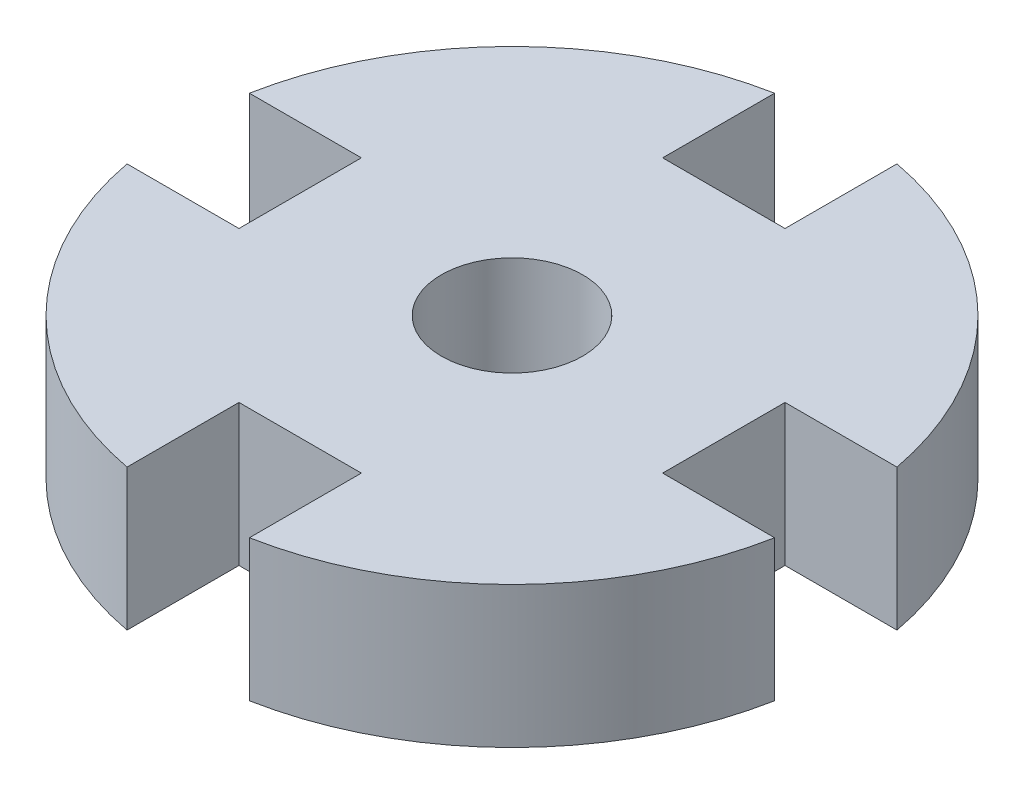
SolidWorks part; units mm, degrees
ref_plane "Front Plane" through (0, 0, 0) normal (0, 0, 1) x (1, 0, 0)
ref_plane "Top Plane" through (0, 0, 0) normal (0, 1, 0) x (1, 0, 0)
ref_plane "Right Plane" through (0, 0, 0) normal (1, 0, 0) x (0, 0, -1)
sketch "Sketch1" plane through (0, 0, 0) normal (0, 1, 0) x (1, 0, 0)
  circle A0 centre (0, 0) radius 1.5
  circle A2 centre (0, 0) radius 7
  dimension "D1" = 3
  dimension "D2" = 14
extrude "Boss-Extrude1" add sketch "Sketch1" along normal blind 1.5 and the other way blind 1.5
sketch "Sketch2" plane through (0, 1.5, 0) normal (0, 1, 0) x (1, 0, 0)
  line L1 (9.5, -1.3) -> (4.5, -1.3)
  line L2 (9.5, -1.3) -> (9.5, 1.3)
  line L3 (9.5, 1.3) -> (4.5, 1.3)
  line L4 (4.5, -1.3) -> (4.5, 1.3)
  line L5 (7, 1.3) -> (7, -1.3) construction
  line L6 (9.5, 0) -> (4.5, 0) construction
  circle A0 centre (0, 0) radius 7 construction
  point P0 (7, 0)
  dimension "D1" = 2.6
  dimension "D2" = 2.5
extrude "Cut-Extrude1" cut sketch "Sketch2" against normal through all
pattern_circular "CirPattern1" count 4 over 360 about axis through (0, -1.5, 0) along (0, 1, 0) of "Cut-Extrude1" reverse direction yes
